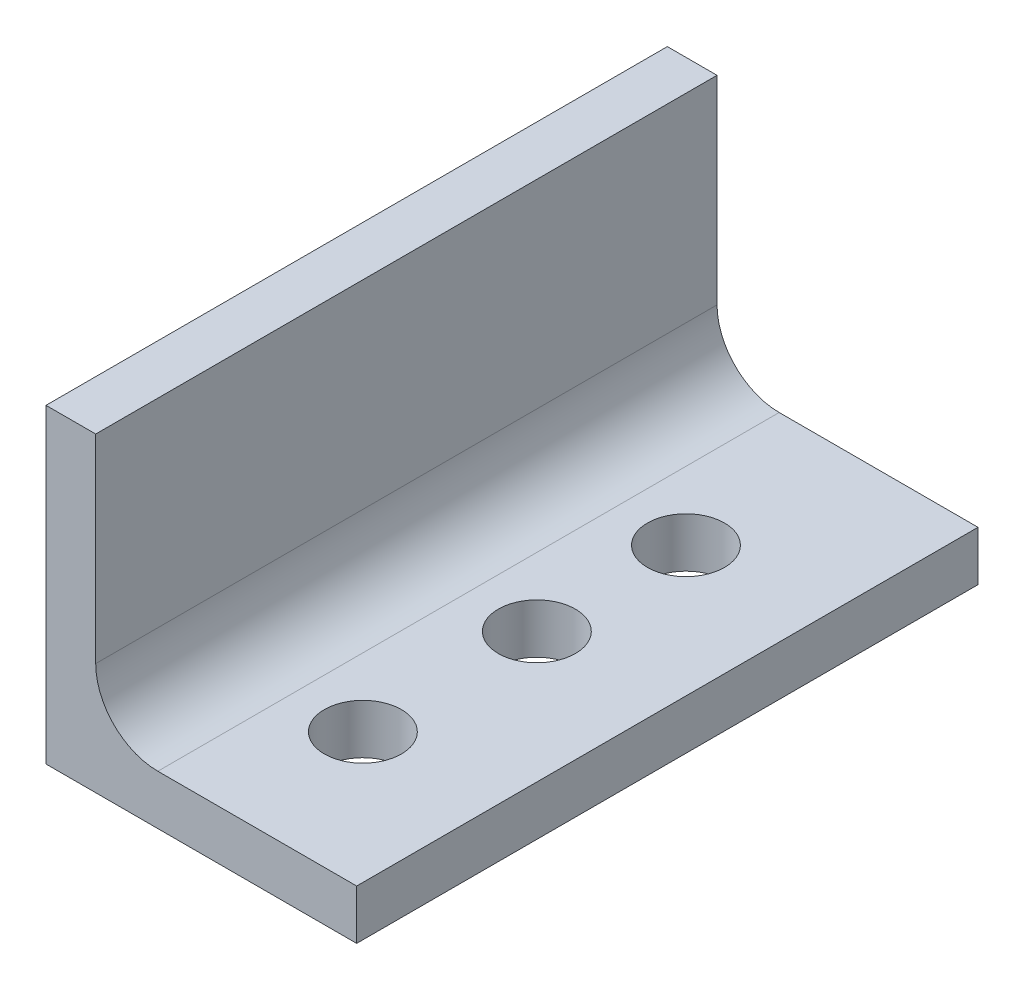
SolidWorks part; units mm, degrees
ref_plane "Front Plane" through (0, 0, 0) normal (0, 0, 1) x (1, 0, 0)
ref_plane "Top Plane" through (0, 0, 0) normal (0, 1, 0) x (1, 0, 0)
ref_plane "Right Plane" through (0, 0, 0) normal (1, 0, 0) x (0, 0, -1)
sketch "Sketch1" plane through (0, 0, 0) normal (0, 0, 1) x (1, 0, 0)
  line L0 (-6.35, 6.35) -> (-6.35, 0)
  line L1 (-6.35, 0) -> (0, 0)
  line L2 (-5.334, 6.35) -> (-5.334, 1.016)
  line L3 (-5.334, 1.016) -> (0, 1.016)
  line L4 (-5.334, 6.35) -> (-6.35, 6.35)
  line L5 (0, 1.016) -> (0, 0)
  dimension "D1" = 6.35
  dimension "D2" = 6.35
  dimension "D3" = 1.016
extrude "Boss-Extrude1" add sketch "Sketch1" along normal blind 12.7
sketch "Sketch3" plane through (0, 1.016, 0) normal (0, 1, 0) x (1, 0, 0)
  line L0 (-2.667, 0) -> (-2.667, -12.7) construction
  line L1 (0, 0) -> (-5.334, 0) construction
  line L3 (0, -12.7) -> (-5.334, -12.7) construction
  line L4 (0, -6.35) -> (-5.334, -6.35) construction
  line L5 (0, -12.7) -> (0, 0) construction
  line L6 (-5.334, -12.7) -> (-5.334, 0) construction
  circle A0 centre (-2.667, -9.906) radius 0.7874
  circle A1 centre (-2.667, -6.35) radius 0.7874
  circle A2 centre (-2.667, -3.302) radius 0.7874
  dimension "D1" = 1.5748
  dimension "D2" = 3.556
  dimension "D3" = 3.048
extrude "Cut-Extrude1" cut sketch "Sketch3" against normal blind 2.54
fillet "Fillet1" radius 1.27 1 edges at (-5.334, 1.016, 6.35)
